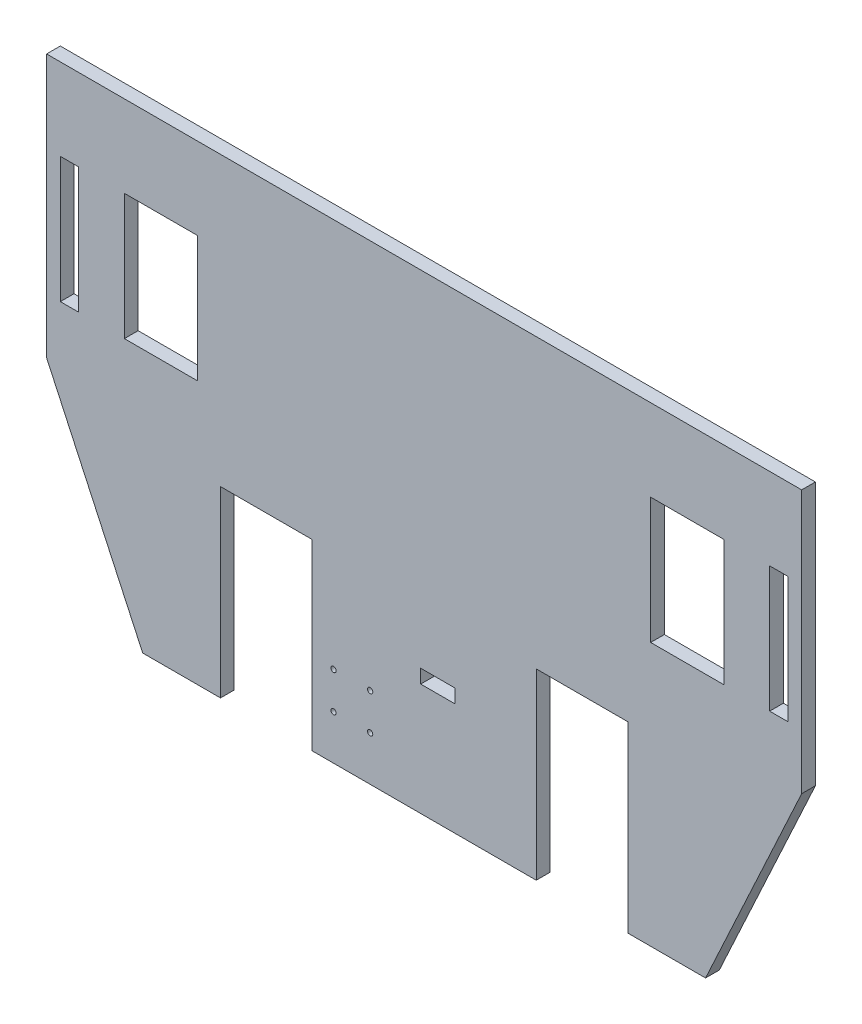
SolidWorks part; units mm, degrees
ref_plane "Plan de face" through (0, 0, 0) normal (0, 0, 1) x (1, 0, 0)
ref_plane "Plan de dessus" through (0, 0, 0) normal (0, 1, 0) x (1, 0, 0)
ref_plane "Plan de droite" through (0, 0, 0) normal (1, 0, 0) x (0, 0, -1)
sketch "Esquisse1" plane through (0, 0, 0) normal (0, 0, 1) x (1, 0, 0)
  line L0 (0, 124.9429) -> (0, -204.46) construction
  line L1 (-165, 96.73) -> (165, 96.73)
  line L2 (165, 96.73) -> (165, -18.27)
  line L3 (165, -18.27) -> (123, -109.0224)
  line L4 (123, -109.0224) -> (-123, -109.0224)
  line L5 (-211.9802, 0) -> (248.5953, 0) construction
  line L6 (-123, -109.0224) -> (-165, -18.27)
  line L7 (-165, -18.27) -> (-165, 96.73)
  line L9 (13.5, -54.0224) -> (-1.5, -54.0224)
  line L10 (13.5, -54.0224) -> (13.5, -60.0224)
  line L11 (13.5, -60.0224) -> (-1.5, -60.0224)
  line L12 (-1.5, -54.0224) -> (-1.5, -60.0224)
  circle A0 centre (-23.6, -89.5224) radius 1.15
  circle A1 centre (-23.6, -73.5224) radius 1.15
  circle A2 centre (-39.6, -89.5224) radius 1.15
  circle A3 centre (-39.6, -73.5224) radius 1.15
  dimension "D15" = 2.3
  dimension "D16" = 2.3
  dimension "D17" = 2.3
  dimension "D18" = 2.3
  dimension "D24" = 83.4
  dimension "D2" = 165
  dimension "D3" = 330
  dimension "D4" = 100
  dimension "D5" = 115
  dimension "D6" = 100
  dimension "D7" = 246
  dimension "D8" = 205.7524
  dimension "D9" = 96.73
  dimension "D10" = 115
  dimension "D11" = 6
  dimension "D12" = 15
  dimension "D13" = 49
  dimension "D14" = 109.5
  dimension "D19" = 19.5
  dimension "D20" = 16
  dimension "D21" = 16
  dimension "D22" = 16
  dimension "D23" = 16
extrude "Boss.-Extru.1" add sketch "Esquisse1" along normal blind 6
sketch "Esquisse2" plane through (0, 0, 6) normal (0, 0, 1) x (1, 0, 0)
  line L0 (-123, -109.0224) -> (123, -109.0224) construction
  line L1 (-159, 60.9776) -> (-151, 60.9776)
  line L2 (-159, 60.9776) -> (-159, 5.9776)
  line L3 (-159, 5.9776) -> (-151, 5.9776)
  line L4 (-151, 60.9776) -> (-151, 5.9776)
  line L5 (-131, 60.9776) -> (-99, 60.9776)
  line L6 (-131, 60.9776) -> (-131, 5.9776)
  line L7 (-131, 5.9776) -> (-99, 5.9776)
  line L8 (-99, 60.9776) -> (-99, 5.9776)
  line L9 (0, 145.0258) -> (0, -189.2208) construction
  line L10 (99, 60.9776) -> (99, 5.9776)
  line L11 (131, 5.9776) -> (99, 5.9776)
  line L12 (131, 60.9776) -> (131, 5.9776)
  line L13 (131, 60.9776) -> (99, 60.9776)
  line L14 (151, 60.9776) -> (151, 5.9776)
  line L15 (159, 5.9776) -> (151, 5.9776)
  line L16 (159, 60.9776) -> (159, 5.9776)
  line L17 (159, 60.9776) -> (151, 60.9776)
  line L19 (89, -109.0224) -> (89, -29.0224)
  line L20 (-49, -109.0224) -> (-89, -109.0224)
  line L21 (-49, -109.0224) -> (-49, -29.0224)
  line L22 (-49, -29.0224) -> (-89, -29.0224)
  line L23 (-89, -109.0224) -> (-89, -29.0224)
  line L24 (49, -29.0224) -> (89, -29.0224)
  line L25 (49, -109.0224) -> (49, -29.0224)
  line L26 (49, -109.0224) -> (89, -109.0224)
  line L27 (-165, 96.73) -> (-165, -18.27) construction
  line L28 (-123, -109.0224) -> (123, -109.0224) construction
  dimension "D2" = 8
  dimension "D3" = 20
  dimension "D4" = 32
  dimension "D5" = 99
  dimension "D6" = 55
  dimension "D7" = 55
  dimension "D8" = 115
  dimension "D9" = 115
  dimension "D10" = 40
  dimension "D11" = 80
  dimension "D12" = 76
  dimension "D13" = 98
  dimension "D14" = 6
  dimension "D15" = 0
extrude "Enlèv. mat.-Extru.1" cut sketch "Esquisse2" against normal blind 6
